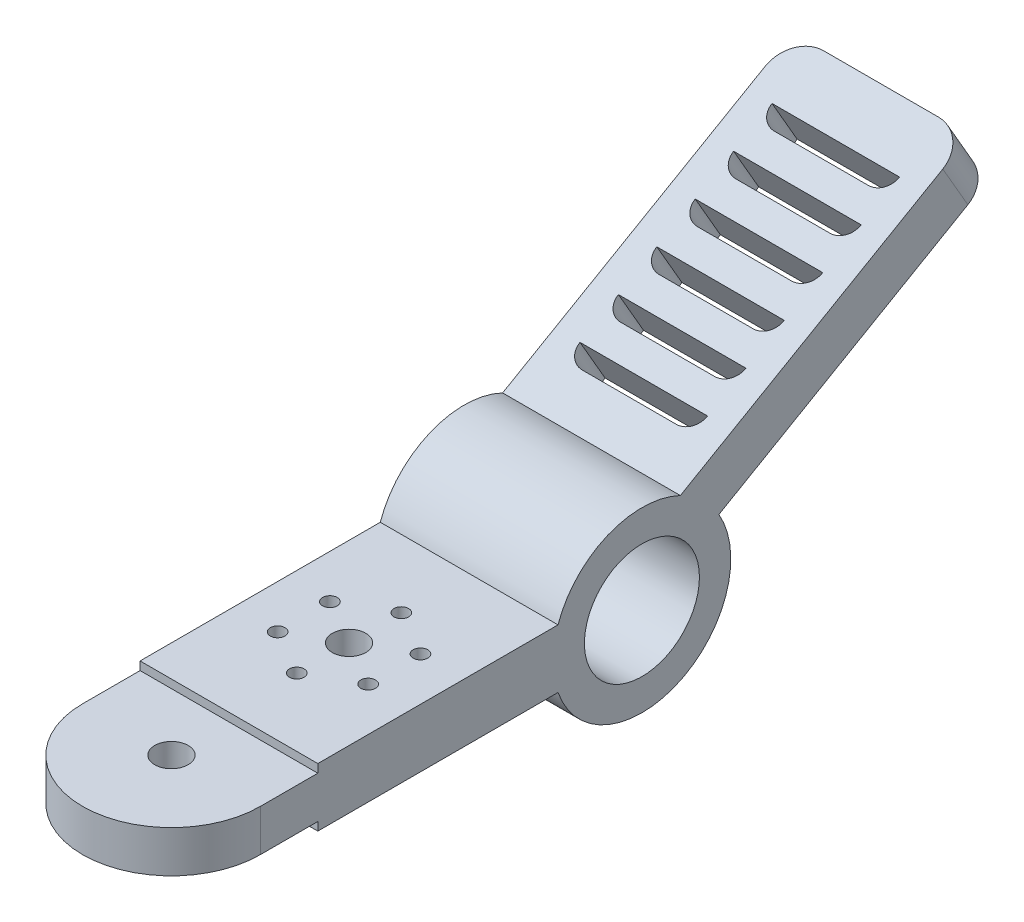
SolidWorks part; units mm, degrees
material "1345 합금"
ref_plane "정면" through (0, 0, 0) normal (0, 0, 1) x (1, 0, 0)
ref_plane "윗면" through (0, 0, 0) normal (0, 1, 0) x (1, 0, 0)
ref_plane "우측면" through (0, 0, 0) normal (1, 0, 0) x (0, 0, -1)
sketch "Sketch1" plane through (0, 0, 0) normal (1, 0, 0) x (0, 0, -1)
  line L0 (-302.9495, 0) -> (-225, 0) construction
  line L1 (0, 0) -> (168.875, 97.5)
  line L2 (-12, 20.7846) -> (156.875, 118.2846)
  line L3 (0, 0) -> (-12, 20.7846)
  line L4 (168.875, 97.5) -> (156.875, 118.2846)
  line L6 (0, 14) -> (-155, 14)
  line L7 (0, -14) -> (-155, -14)
  line L8 (0, 14) -> (0, -14)
  line L9 (-155, 14) -> (-155, 10)
  line L12 (-155, -10) -> (-225, -10)
  line L13 (0, 10) -> (0, -10)
  line L14 (-225, 10) -> (-225, -10)
  line L18 (0, 0) -> (135.4704, 0) construction
  line L19 (-155, 10) -> (-225, 10)
  line L21 (-155, -10) -> (-155, -14)
  circle A0 centre (0, 0) radius 42.5
  point P8 (0, 0)
  point P18 (0, 0)
  dimension "D8" = 85
  dimension "D1" = 30
  dimension "D2" = 195
  dimension "D6" = 155
  dimension "D7" = 225
  dimension "D4" = 28
  dimension "D5" = 20
  dimension "D3" = 24
extrude "Boss-Extrude1" add sketch "Sketch1" along normal blind 85 contours A0 L6 L9 L19 L14 L12 L21 L7 | L7 A0 L1 L8 | L6 A0 L7 L8 L3 | L2 A0 L6 L3 | L8 L6 L3 | L1 A0 L2 L3 L6 L8 | A0 L1 L4 L2 region at (0, 20.812, -12.4972) region at (0, -0.4751, 21.7901) region at (0, 9.3333, 2.6943) region at (0, -16.03, -9.1636) region at (0, 69.2456, -95.749) region at (0, 28.4168, 13.6532) region at (0, 0, 126.4198)
hole_wizard "Ø16.0 (55) Diameter Hole1" positions "3DSketch1" profile "Sketch2" hole size "Ø16.0" standard "Ansi Metric" end condition up to next
sketch3d "3DSketch1"
  line L0 (85, 0, 0) -> (0, 0, 0) construction
  point P0 (85, 0, 0)
sketch "Sketch2" plane through (85, 0, 0) normal (0, 1, 0) x (0, 0, -1)
  line L0 (0, 0) -> (0, 85)
  line L1 (0, 85) -> (27.5, 85)
  line L2 (27.5, 85) -> (27.5, 0)
  line L5 (27.5, 0) -> (0, 0)
  line L11 (0, -6.35) -> (0, 107.95) construction
  dimension "관통 구멍 지름" = 55
  dimension "관통 구멍 깊이" = 85
sketch "Sketch3" plane through (0, 20.7846, 12) normal (0, 0.866, 0.5) x (1, 0, 0)
  line L0 (85, 195) -> (0, 195) construction
  line L1 (12, 170) -> (73, 170)
  line L2 (12, 170) -> (12, 169.999)
  line L3 (20, 161.999) -> (65, 161.999)
  line L4 (73, 170) -> (73, 169.999)
  line L5 (42.5, 195) -> (42.5, 169.2831) construction
  line L6 (12, 148.79) -> (12, 148.789)
  line L7 (12, 148.79) -> (73, 148.79)
  line L8 (73, 148.79) -> (73, 148.789)
  line L9 (20, 140.789) -> (65, 140.789)
  line L10 (12, 127.58) -> (12, 127.579)
  line L11 (12, 127.58) -> (73, 127.58)
  line L12 (73, 127.58) -> (73, 127.579)
  line L13 (20, 119.579) -> (65, 119.579)
  line L14 (12, 106.37) -> (12, 106.369)
  line L15 (12, 106.37) -> (73, 106.37)
  line L16 (73, 106.37) -> (73, 106.369)
  line L17 (20, 98.369) -> (65, 98.369)
  line L18 (12, 85.16) -> (12, 85.159)
  line L19 (12, 85.16) -> (73, 85.16)
  line L20 (73, 85.16) -> (73, 85.159)
  line L21 (20, 77.159) -> (65, 77.159)
  line L22 (12, 63.95) -> (12, 63.949)
  line L23 (12, 63.95) -> (73, 63.95)
  line L24 (73, 63.95) -> (73, 63.949)
  line L25 (20, 55.949) -> (65, 55.949)
  arc A0 (12, 169.999) -> (20, 161.999) centre (20, 169.999) ccw
  arc A1 (73, 169.999) -> (65, 161.999) centre (65, 169.999) cw
  arc A2 (12, 148.789) -> (20, 140.789) centre (20, 148.789) ccw
  arc A3 (73, 148.789) -> (65, 140.789) centre (65, 148.789) cw
  arc A4 (12, 127.579) -> (20, 119.579) centre (20, 127.579) ccw
  arc A5 (73, 127.579) -> (65, 119.579) centre (65, 127.579) cw
  arc A6 (12, 106.369) -> (20, 98.369) centre (20, 106.369) ccw
  arc A7 (73, 106.369) -> (65, 98.369) centre (65, 106.369) cw
  arc A8 (12, 85.159) -> (20, 77.159) centre (20, 85.159) ccw
  arc A9 (73, 85.159) -> (65, 77.159) centre (65, 85.159) cw
  arc A10 (12, 63.949) -> (20, 55.949) centre (20, 63.949) ccw
  arc A11 (73, 63.949) -> (65, 55.949) centre (65, 63.949) cw
  point P8 (42.5, 170)
  point P13 (73, 161.999)
  point P14 (0, 0)
  point P15 (0, 0)
  point P56 (0, 0)
  dimension "D3" = 8
  dimension "D1" = 25
  dimension "D2" = 8.001
  dimension "D4" = 61
  dimension "D5" = 6
extrude "Cut-Extrude1" cut sketch "Sketch3" against normal blind 85 contours A5 L12 L11 L10 A4 L13 | A7 L16 L15 L14 A6 L17 | A9 L20 L19 L18 A8 L21 | A11 L24 L23 L22 A10 L25 | L1 L4 A1 L3 A0 L2 | L7 L8 A3 L9 A2 L6 region at (42.5, 82.6404, -95.1373) region at (42.5, 72.0354, -76.7689) region at (42.5, 61.4304, -58.4005) region at (42.5, 50.8254, -40.0321)
fillet "Fillet1" 2 edges at (85, 0, 225) (0, 0, 225) type full round first side face at (85, 0, -27.5) second side face at (0, 0, -27.5) middle face at (42.5, 0, 225)
hole_wizard "Ø16.0 (16) Diameter Hole1" positions "3DSketch3" profile "Sketch5" hole size "Ø16.0" standard "Ansi Metric" end condition up to next
sketch3d "3DSketch3"
  line L0 (42.5, 10, 182.5) -> (42.5, -10, 182.5) construction
  point P0 (42.5, -10, 182.5)
sketch "Sketch5" plane through (42.5, -10, 182.5) normal (1, 0, 0) x (0, 0, -1)
  line L0 (0, 0) -> (0, 20)
  line L1 (0, 20) -> (8, 20)
  line L2 (8, 20) -> (8, 0)
  line L5 (8, 0) -> (0, 0)
  line L11 (0, -6.35) -> (0, 107.95) construction
  dimension "관통 구멍 지름" = 16
  dimension "관통 구멍 깊이" = 20
hole_wizard "Ø16.0 (16) Diameter Hole2" positions "3DSketch5" profile "Sketch7" hole size "Ø16.0" standard "Ansi Metric" end condition up to next
sketch3d "3DSketch5"
  line L0 (85, 14, 155) -> (0, 14, 155) construction
  line L1 (0, 14, 40.1279) -> (0, 14, 155) construction
  point P0 (42.5, 14, 97.564)
  point P5 (42.5, 14, 155)
  point P8 (0, 14, 97.564)
sketch "Sketch7" plane through (42.5, 14, 97.564) normal (1, 0, 0) x (0, 0, 1)
  line L0 (0, 0) -> (0, 28)
  line L1 (0, 28) -> (8, 28)
  line L2 (8, 28) -> (8, 0)
  line L5 (8, 0) -> (0, 0)
  line L11 (0, -6.35) -> (0, 107.95) construction
  dimension "관통 구멍 지름" = 16
  dimension "관통 구멍 깊이" = 28
sketch "Sketch9" plane through (0, 14, 0) normal (0, 1, 0) x (1, 0, 0)
  circle A0 centre (42.5, -97.564) radius 25 construction
  circle A1 centre (42.5, -72.564) radius 3.5
  circle A2 centre (64.1506, -85.064) radius 3.5
  circle A3 centre (64.1506, -110.064) radius 3.5
  circle A4 centre (42.5, -122.564) radius 3.5
  circle A5 centre (20.8494, -110.064) radius 3.5
  circle A6 centre (20.8494, -85.064) radius 3.5
  point P5 (0, 0)
  point P18 (42.5, -97.564)
  dimension "D1" = 50
  dimension "D2" = 7
  dimension "D3" = 6
extrude "Cut-Extrude2" cut sketch "Sketch9" against normal blind 85
fillet "Fillet2" radius 15 2 edges at (85, 107.8923, -162.875) (0, 107.8923, -162.875)
